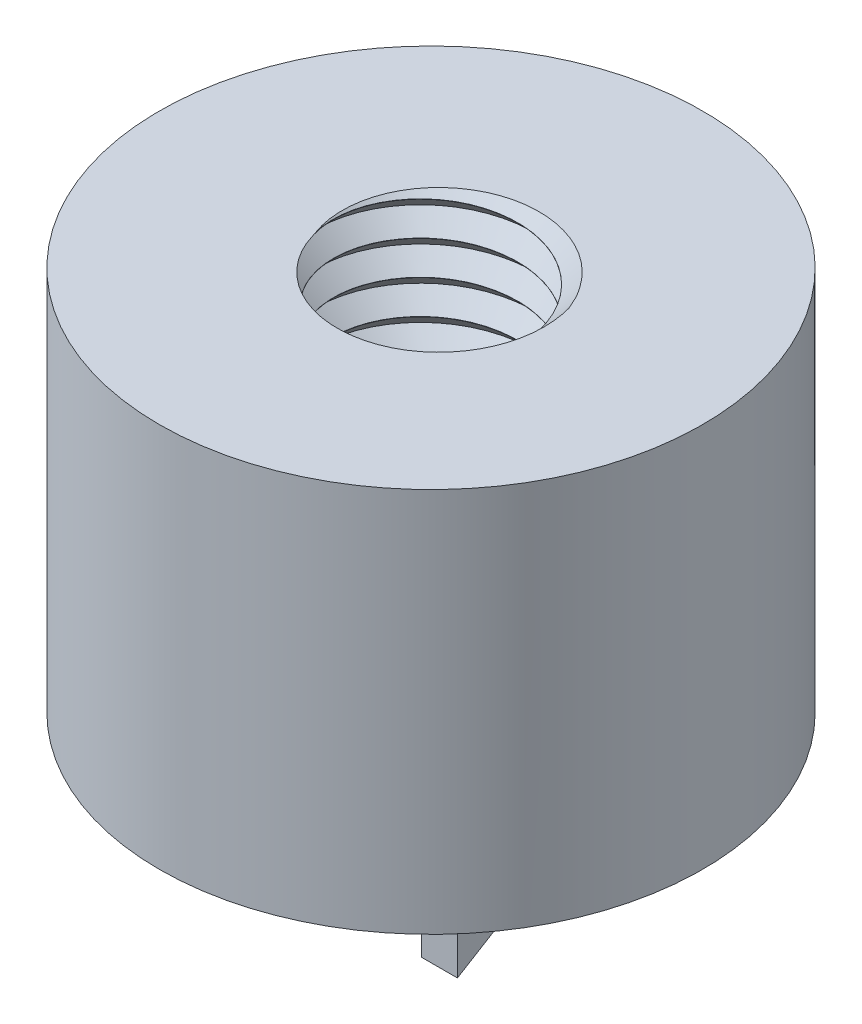
SolidWorks part; units mm, degrees
other "Markup1"
sketch "Sketch7" plane through (8, -40.1821, 8) normal (0.788, -0.5726, 0.226) x (0.2068, -0.0996, -0.9733)
other "Markup2"
sketch "Sketch8" plane through (10, -42.1821, -10) normal (0.2153, -0.7341, -0.6439) x (-0.8854, 0.1314, -0.4459)
material "7075-T6，板材(SS)"
ref_plane "前视基准面" through (0, 0, 0) normal (0, 0, 1) x (1, 0, 0)
ref_plane "上视基准面" through (0, 0, 0) normal (0, 1, 0) x (1, 0, 0)
ref_plane "右视基准面" through (0, 0, 0) normal (1, 0, 0) x (0, 0, -1)
sketch "草图1" plane through (0, 0, 0) normal (0, 0, 1) x (1, 0, 0)
  line L0 (0, 16.878) -> (0, -16.878) construction
  line L1 (0, 0) -> (3.4, 0) construction
  line L3 (3.4, 0) -> (10, 0)
  line L4 (3.4, 0) -> (3.4, -11)
  line L5 (3.4, -11) -> (10, -11)
  line L6 (10, 0) -> (10, -11)
  point P4 (0, 0)
  dimension "D1" = 3.4
  dimension "D2" = 10
  dimension "D3" = 11
revolve "旋转1" add sketch "草图1" angle 360 about L0
sketch "草图2" plane through (0, -11, 0) normal (0, -1, 0) x (1, 0, 0)
  circle A0 centre (0, 0) radius 3.4 construction
  circle A1 centre (0, 0) radius 3.4
curve "螺旋线/涡状线1" pitch 1.25 height 12.8125 radius 3.4 centre (0, -11, 0) axis (0, 1, 0) start towards (0, 0, -1)
sketch "草图3" plane through (0, 0, 0) normal (1, 0, 0) x (0, 0, -1)
  line L0 (3.4, -11.62) -> (3.4, -10.38)
  line L1 (3.4, -10.38) -> (4.025, -11)
  line L2 (-10, -11) -> (10, -11) construction
  line L3 (0, 0) -> (0, -13.2999) construction
  line L4 (-10, -11) -> (10, -11) construction
  line L5 (3.4, -11.62) -> (4.025, -11)
  spline S0 degree 3 poles (-1995.5188, 50.9214) (-241.4894, -14.1354) (17.2925, -12.3735) (2.4668, -10.8438) (1.335, -10.7656) (0, -10.6875) (-1.335, -10.6094) (-2.4668, -10.5313) (-3.223, -10.4531) (-3.4885, -10.375) (-3.223, -10.2969) (-2.4668, -10.2188) (-0.9577, -10.1146) (0.9577, -10.0104) (2.4668, -9.9063) (3.223, -9.8281) (3.4885, -9.75) (3.223, -9.6719) (2.4668, -9.5938) (0.9577, -9.4896) (-0.9577, -9.3854) (-2.4668, -9.2812) (-3.223, -9.2031) (-3.4885, -9.125) (-3.223, -9.0469) (-2.4668, -8.9687) (-0.9577, -8.8646) (0.9577, -8.7604) (2.4668, -8.6562) (3.223, -8.5781) (3.4885, -8.5) (3.223, -8.4219) (2.4668, -8.3437) (0.9577, -8.2396) (-0.9577, -8.1354) (-2.4668, -8.0312) (-3.223, -7.9531) (-3.4885, -7.875) (-3.223, -7.7969) (-2.4668, -7.7187) (-0.9577, -7.6146) (0.9577, -7.5104) (2.4668, -7.4062) (3.223, -7.3281) (3.4885, -7.25) (3.223, -7.1719) (2.4668, -7.0937) (0.9577, -6.9896) (-0.9577, -6.8854) (-2.4668, -6.7812) (-3.223, -6.7031) (-3.4885, -6.625) (-3.223, -6.5469) (-2.4668, -6.4687) (-0.9577, -6.3646) (0.9577, -6.2604) (2.4668, -6.1562) (3.223, -6.0781) (3.4885, -6) (3.223, -5.9219) (2.4668, -5.8437) (0.9577, -5.7396) (-0.9577, -5.6354) (-2.4668, -5.5312) (-3.223, -5.4531) (-3.4885, -5.375) (-3.223, -5.2969) (-2.4668, -5.2187) (-0.9577, -5.1146) (0.9577, -5.0104) (2.4668, -4.9062) (3.223, -4.8281) (3.4885, -4.75) (3.223, -4.6719) (2.4668, -4.5937) (0.9577, -4.4896) (-0.9577, -4.3854) (-2.4668, -4.2812) (-3.223, -4.2031) (-3.4885, -4.125) (-3.223, -4.0469) (-2.4668, -3.9687) (-0.9577, -3.8646) (0.9577, -3.7604) (2.4668, -3.6562) (3.223, -3.5781) (3.4885, -3.5) (3.223, -3.4219) (2.4668, -3.3437) (0.9577, -3.2396) (-0.9577, -3.1354) (-2.4668, -3.0312) (-3.223, -2.9531) (-3.4885, -2.875) (-3.223, -2.7969) (-2.4668, -2.7187) (-0.9577, -2.6146) (0.9577, -2.5104) (2.4668, -2.4062) (3.223, -2.3281) (3.4885, -2.25) (3.223, -2.1719) (2.4668, -2.0937) (0.9577, -1.9896) (-0.9577, -1.8854) (-2.4668, -1.7812) (-3.223, -1.7031) (-3.4885, -1.625) (-3.223, -1.5469) (-2.4668, -1.4687) (-0.9577, -1.3646) (0.9577, -1.2604) (2.4668, -1.1562) (3.223, -1.0781) (3.4885, -1) (3.223, -0.9219) (2.4668, -0.8437) (0.9577, -0.7396) (-0.9577, -0.6354) (-2.4668, -0.5312) (-3.223, -0.4531) (-3.4885, -0.375) (-3.223, -0.2969) (-2.4668, -0.2187) (-0.9577, -0.1146) (0.9577, -0.0104) (2.4668, 0.0938) (3.223, 0.1719) (3.4885, 0.25) (3.223, 0.3281) (2.4668, 0.4063) (0.9577, 0.5104) (-0.9577, 0.6146) (-2.4668, 0.7188) (-3.223, 0.7969) (-3.4885, 0.875) (-3.223, 0.9531) (-2.4668, 1.0313) (-0.9577, 1.1354) (0.9577, 1.2396) (2.4668, 1.3438) (3.223, 1.4219) (3.4885, 1.5) (3.2231, 1.5781) (2.4664, 1.6563) (-12.6096, 2.6972) (-80.8528, 3.8297) (1999.6627, -15.0448) knots -0.34034 -0.34034 -0.34034 -0.34034 0.006098 0.012195 0.018293 0.02439 0.030488 0.036585 0.042683 0.04878 0.054878 0.060976 0.067073 0.079268 0.085366 0.091463 0.097561 0.103659 0.109756 0.115854 0.128049 0.134146 0.140244 0.146341 0.152439 0.158537 0.164634 0.176829 0.182927 0.189024 0.195122 0.20122 0.207317 0.213415 0.22561 0.231707 0.237805 0.243902 0.25 0.256098 0.262195 0.27439 0.280488 0.286585 0.292683 0.29878 0.304878 0.310976 0.323171 0.329268 0.335366 0.341463 0.347561 0.353659 0.359756 0.371951 0.378049 0.384146 0.390244 0.396341 0.402439 0.408537 0.420732 0.426829 0.432927 0.439024 0.445122 0.45122 0.457317 0.469512 0.47561 0.481707 0.487805 0.493902 0.5 0.506098 0.518293 0.52439 0.530488 0.536585 0.542683 0.54878 0.554878 0.567073 0.573171 0.579268 0.585366 0.591463 0.597561 0.603659 0.615854 0.621951 0.628049 0.634146 0.640244 0.646341 0.652439 0.664634 0.670732 0.676829 0.682927 0.689024 0.695122 0.70122 0.713415 0.719512 0.72561 0.731707 0.737805 0.743902 0.75 0.762195 0.768293 0.77439 0.780488 0.786585 0.792683 0.79878 0.810976 0.817073 0.823171 0.829268 0.835366 0.841463 0.847561 0.859756 0.865854 0.871951 0.878049 0.884146 0.890244 0.896341 0.908537 0.914634 0.920732 0.926829 0.932927 0.939024 0.945122 0.957317 0.963415 0.969512 0.97561 0.981707 0.987805 0.993902 1.225736 1.225736 1.225736 1.225736 only from (3.4, -11) to (0, 1.8125) construction
  spline S1 degree 3 poles (3.4, -11) (3.4, -10.9741) (3.223, -10.9218) (2.4668, -10.8438) (1.335, -10.7656) (0, -10.6875) (-1.335, -10.6094) (-2.4668, -10.5313) (-3.223, -10.4531) (-3.4885, -10.375) (-3.223, -10.2969) (-2.4668, -10.2188) (-0.9577, -10.1146) (0.9577, -10.0104) (2.4668, -9.9063) (3.223, -9.8281) (3.4885, -9.75) (3.223, -9.6719) (2.4668, -9.5938) (0.9577, -9.4896) (-0.9577, -9.3854) (-2.4668, -9.2812) (-3.223, -9.2031) (-3.4885, -9.125) (-3.223, -9.0469) (-2.4668, -8.9687) (-0.9577, -8.8646) (0.9577, -8.7604) (2.4668, -8.6562) (3.223, -8.5781) (3.4885, -8.5) (3.223, -8.4219) (2.4668, -8.3437) (0.9577, -8.2396) (-0.9577, -8.1354) (-2.4668, -8.0312) (-3.223, -7.9531) (-3.4885, -7.875) (-3.223, -7.7969) (-2.4668, -7.7187) (-0.9577, -7.6146) (0.9577, -7.5104) (2.4668, -7.4062) (3.223, -7.3281) (3.4885, -7.25) (3.223, -7.1719) (2.4668, -7.0937) (0.9577, -6.9896) (-0.9577, -6.8854) (-2.4668, -6.7812) (-3.223, -6.7031) (-3.4885, -6.625) (-3.223, -6.5469) (-2.4668, -6.4687) (-0.9577, -6.3646) (0.9577, -6.2604) (2.4668, -6.1562) (3.223, -6.0781) (3.4885, -6) (3.223, -5.9219) (2.4668, -5.8437) (0.9577, -5.7396) (-0.9577, -5.6354) (-2.4668, -5.5312) (-3.223, -5.4531) (-3.4885, -5.375) (-3.223, -5.2969) (-2.4668, -5.2187) (-0.9577, -5.1146) (0.9577, -5.0104) (2.4668, -4.9062) (3.223, -4.8281) (3.4885, -4.75) (3.223, -4.6719) (2.4668, -4.5937) (0.9577, -4.4896) (-0.9577, -4.3854) (-2.4668, -4.2812) (-3.223, -4.2031) (-3.4885, -4.125) (-3.223, -4.0469) (-2.4668, -3.9687) (-0.9577, -3.8646) (0.9577, -3.7604) (2.4668, -3.6562) (3.223, -3.5781) (3.4885, -3.5) (3.223, -3.4219) (2.4668, -3.3437) (0.9577, -3.2396) (-0.9577, -3.1354) (-2.4668, -3.0312) (-3.223, -2.9531) (-3.4885, -2.875) (-3.223, -2.7969) (-2.4668, -2.7187) (-0.9577, -2.6146) (0.9577, -2.5104) (2.4668, -2.4062) (3.223, -2.3281) (3.4885, -2.25) (3.223, -2.1719) (2.4668, -2.0937) (0.9577, -1.9896) (-0.9577, -1.8854) (-2.4668, -1.7812) (-3.223, -1.7031) (-3.4885, -1.625) (-3.223, -1.5469) (-2.4668, -1.4687) (-0.9577, -1.3646) (0.9577, -1.2604) (2.4668, -1.1562) (3.223, -1.0781) (3.4885, -1) (3.223, -0.9219) (2.4668, -0.8437) (0.9577, -0.7396) (-0.9577, -0.6354) (-2.4668, -0.5312) (-3.223, -0.4531) (-3.4885, -0.375) (-3.223, -0.2969) (-2.4668, -0.2187) (-0.9577, -0.1146) (0.9577, -0.0104) (2.4668, 0.0938) (3.223, 0.1719) (3.4885, 0.25) (3.223, 0.3281) (2.4668, 0.4063) (0.9577, 0.5104) (-0.9577, 0.6146) (-2.4668, 0.7188) (-3.223, 0.7969) (-3.4885, 0.875) (-3.223, 0.9531) (-2.4668, 1.0313) (-0.9577, 1.1354) (0.9577, 1.2396) (2.4668, 1.3438) (3.223, 1.4219) (3.4885, 1.5) (3.2231, 1.5781) (2.4664, 1.6563) (1.3363, 1.7343) (0.4422, 1.7866) (0, 1.8125) knots 0 0 0 0 0.006098 0.012195 0.018293 0.02439 0.030488 0.036585 0.042683 0.04878 0.054878 0.060976 0.067073 0.079268 0.085366 0.091463 0.097561 0.103659 0.109756 0.115854 0.128049 0.134146 0.140244 0.146341 0.152439 0.158537 0.164634 0.176829 0.182927 0.189024 0.195122 0.20122 0.207317 0.213415 0.22561 0.231707 0.237805 0.243902 0.25 0.256098 0.262195 0.27439 0.280488 0.286585 0.292683 0.29878 0.304878 0.310976 0.323171 0.329268 0.335366 0.341463 0.347561 0.353659 0.359756 0.371951 0.378049 0.384146 0.390244 0.396341 0.402439 0.408537 0.420732 0.426829 0.432927 0.439024 0.445122 0.45122 0.457317 0.469512 0.47561 0.481707 0.487805 0.493902 0.5 0.506098 0.518293 0.52439 0.530488 0.536585 0.542683 0.54878 0.554878 0.567073 0.573171 0.579268 0.585366 0.591463 0.597561 0.603659 0.615854 0.621951 0.628049 0.634146 0.640244 0.646341 0.652439 0.664634 0.670732 0.676829 0.682927 0.689024 0.695122 0.70122 0.713415 0.719512 0.72561 0.731707 0.737805 0.743902 0.75 0.762195 0.768293 0.77439 0.780488 0.786585 0.792683 0.79878 0.810976 0.817073 0.823171 0.829268 0.835366 0.841463 0.847561 0.859756 0.865854 0.871951 0.878049 0.884146 0.890244 0.896341 0.908537 0.914634 0.920732 0.926829 0.932927 0.939024 0.945122 0.957317 0.963415 0.969512 0.97561 0.981707 0.987805 0.993902 1 1 1 1 construction
  dimension "D1" = 4.025
  dimension "D2" = 0.62
sweep "切除-扫描1" cut profiles "草图3" path "螺旋线/涡状线1" align with end faces yes
sketch "草图4" plane through (0, 0, 0) normal (0, 0, 1) x (1, 0, 0)
  line L0 (-10, -11) -> (10, -11) construction
  line L1 (-10, -11) -> (10, -11) construction
  line L2 (0, 0) -> (0, -14.1821) construction
  line L3 (0, -13.3238) -> (4.025, -11)
  line L4 (4.025, -11) -> (10, -11)
  line L10 (0, -13.3238) -> (0, -14.1821)
  line L14 (10, -11) -> (10, -14.1821)
  line L15 (10, -14.1821) -> (0, -14.1821)
  dimension "D1" = 4.025
  dimension "D2" = 60
revolve "旋转2" add sketch "草图4" angle 360 about L2
sketch "草图10" plane through (0, -14.1821, 0) normal (0, -1, 0) x (-1, 0, 0)
  text T0 "A" font "微软雅黑" height 9
extrude "凸台-拉伸1" add sketch "草图10" along normal blind 5
